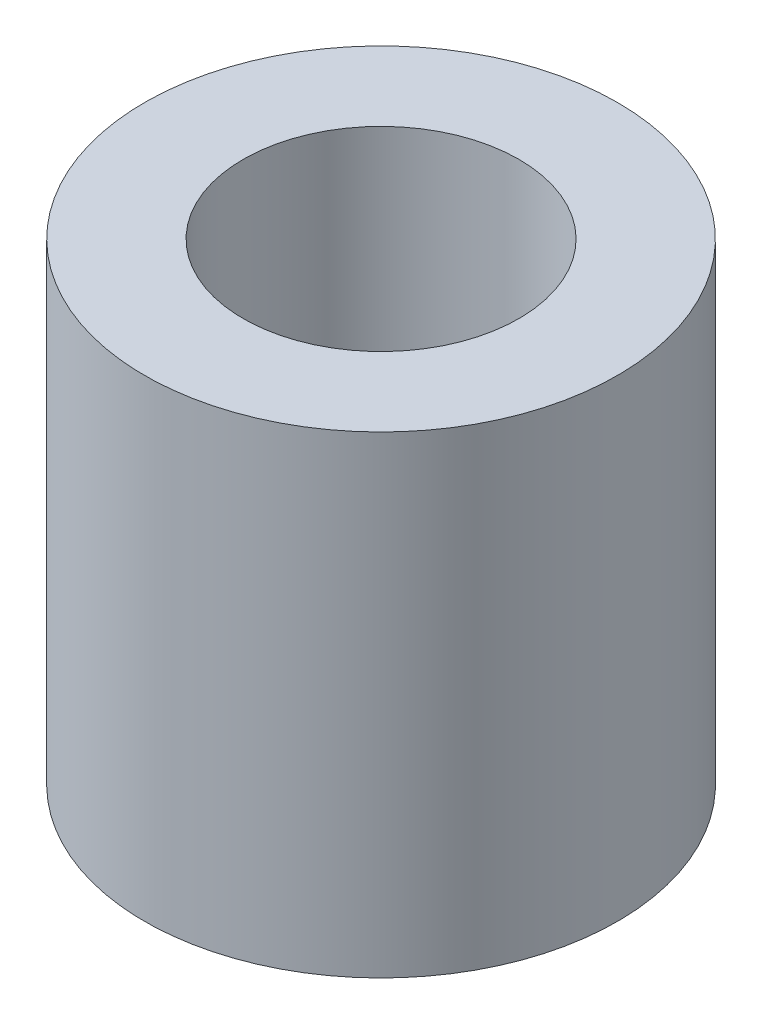
SolidWorks part; units mm, degrees
material "HTPB"
ref_plane "Front Plane" through (0, 0, 0) normal (0, 0, 1) x (1, 0, 0)
ref_plane "Top Plane" through (0, 0, 0) normal (0, 1, 0) x (1, 0, 0)
ref_plane "Right Plane" through (0, 0, 0) normal (1, 0, 0) x (0, 0, -1)
sketch "Sketch1" plane through (0, 0, 0) normal (0, 1, 0) x (1, 0, 0)
  circle A0 centre (0, 0) radius 22.225
  circle A1 centre (0, 0) radius 38.1
  dimension "D1" = 44.45
  dimension "D2" = 76.2
extrude "Boss-Extrude1" add sketch "Sketch1" along normal blind 76.2
